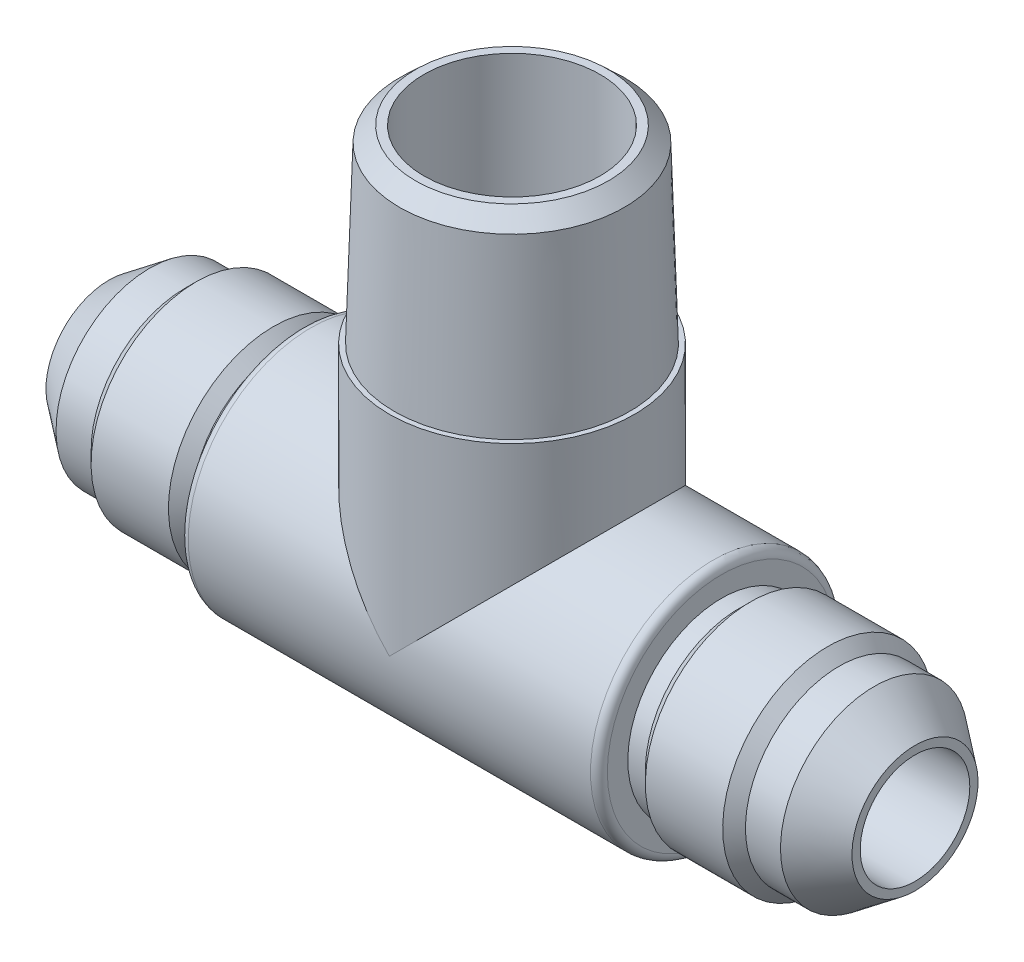
SolidWorks part; units mm, degrees
ref_plane "Front Plane" through (0, 0, 0) normal (0, 0, 1) x (1, 0, 0)
ref_plane "Top Plane" through (0, 0, 0) normal (0, 1, 0) x (1, 0, 0)
ref_plane "Right Plane" through (0, 0, 0) normal (1, 0, 0) x (0, 0, -1)
sketch "Sketch1" plane through (0, 0, 0) normal (0, 0, 1) x (1, 0, 0)
  line L0 (0, 0) -> (-18.9865, 0) construction
  line L1 (0, 0) -> (0, 18.9865) construction
  line L2 (-9.525, 18.9865) -> (9.525, 18.9865) construction
  line L3 (-18.9865, 9.525) -> (-18.9865, -9.525) construction
  line L6 (-36.5125, 9.525) -> (-36.5125, -9.525) construction
  line L8 (-10.668, 36.1163) -> (10.668, 36.1163) construction
  line L9 (0, 0) -> (0, 36.1163) construction
  line L10 (-18.9865, 11.1125) -> (-18.9865, -11.1125) construction
  line L12 (-11.1125, 18.9865) -> (11.1125, 18.9865) construction
  point P15 (0, 22.5603)
  dimension "S" = 17.526
  dimension "Pipe Thread Dia" = 21.336
  dimension "V" = 36.1163
  dimension "TE" = 13.556
  dimension "OA" = 22.225
ref_plane "Plane1" through (-36.5125, 0, 0) normal (1, 0, 0) x (0, 0, -1)
sketch "Sketch2" plane through (-36.5125, 0, 0) normal (1, 0, 0) x (0, 0, -1)
  circle A0 centre (0, 0) radius 9.525
  dimension "Thread OD" = 19.05
extrude "Extrude1" add sketch "Sketch2" along normal up to vertex (17.526 mm away) up to point (-18.9865, 0, 0)
sketch "Sketch3" plane through (-36.5125, 0, 0) normal (-1, 0, 0) x (0, 0, 1)
  circle A0 centre (0, 0) radius 9.525 construction
  circle A1 centre (0, 0) radius 9.525
curve "Helix/Spiral1" pitch 1.5875 height 36.5125 turns 23 parameters "pitch"=1.5875
sketch "Sketch4" plane through (0, 0, 0) normal (0, 0, 1) x (1, 0, 0)
  line L0 (-37.9016, 9.525) -> (-37.3062, 8.4939)
  line L1 (-37.3062, 8.4939) -> (-37.1078, 8.4939)
  line L2 (-37.1078, 8.4939) -> (-36.5125, 9.525)
  line L3 (-37.9016, 9.525) -> (-36.5125, 9.525)
  line L6 (-37.207, 9.525) -> (-37.207, 8.4939) construction
  line L7 (-37.6039, 9.0094) -> (-36.8102, 9.0094) construction
  line L8 (-36.5125, 9.525) -> (-36.5125, -9.525) construction
  dimension "D1" = 0.1984
  dimension "D2" = 0.7937
  dimension "D3" = 60
sweep "Cut-Sweep1" [suppressed] cut profiles "Sketch4" path "Helix/Spiral1"
sketch "Sketch5" plane through (0, 0, 0) normal (0, 0, 1) x (1, 0, 0)
  line L0 (-36.5125, 6.35) -> (-36.5125, -6.35) construction
  line L1 (-32.8189, 8.4939) -> (-29.6439, 8.4939)
  line L2 (-29.6439, 8.4939) -> (-28.6128, 9.525)
  line L3 (-36.5125, 5.7106) -> (-36.5125, -5.7106) construction
  line L4 (-28.6128, 9.525) -> (-36.5125, 9.525)
  line L5 (-37.9016, 9.525) -> (-36.5125, 9.525) construction
  line L6 (-18.9865, 9.525) -> (-18.9865, -9.525) construction
  line L7 (-18.9865, 8.4939) -> (-20.574, 8.4939)
  line L8 (-20.574, 8.4939) -> (-21.6051, 9.525)
  line L9 (-21.6051, 9.525) -> (-18.9865, 9.525)
  line L10 (-18.9865, 8.4939) -> (-18.9865, 9.525)
  line L11 (-27.2626, -9.525) -> (-27.2626, 0) construction
  line L12 (-18.9865, 0) -> (-36.5125, 0) construction
  line L13 (-36.5125, 9.525) -> (-36.5125, -9.525) construction
  line L14 (-36.5125, 5.7106) -> (-32.8189, 8.4939)
  line L15 (-36.5125, 9.525) -> (-36.5125, 5.7106)
  line L16 (0, 0) -> (-18.9865, 0) construction
  point P16 (-27.2626, -9.525)
  dimension "D3" = 45
  dimension "D5" = 45
  dimension "D6" = 1.5875
  dimension "Tube OD" = 12.7
  dimension "D2" = 11.4211
  dimension "D1" = 37
  dimension "D4" = 3.175
  dimension "D7" = 2.3813
revolve "Cut-Revolve1" cut sketch "Sketch5" angle 360 about L0
ref_plane "Plane2" through (-18.9865, 0, 0) normal (1, 0, 0) x (0, 0, -1)
sketch "Sketch15" plane through (-18.9865, 0, 0) normal (1, 0, 0) x (0, 0, -1)
  circle A0 centre (0, 0) radius 11.1125
extrude "Boss-Extrude1" add sketch "Sketch15" along normal up to vertex (18.9865 mm away) up to point (0, 0, 0)
sketch "Sketch16" plane through (0, 0, 0) normal (1, 0, 0) x (0, 0, -1)
  circle A0 centre (0, 0) radius 4.9657
  dimension "Min ID" = 9.9314
extrude "Cut-Extrude1" cut sketch "Sketch16" against normal through all
ref_plane "Plane3" through (0, 18.9865, 0) normal (0, 1, 0) x (-1, 0, 0)
sketch "Sketch20" plane through (0, 18.9865, 0) normal (0, 1, 0) x (-1, 0, 0)
  circle A0 centre (0, 0) radius 11.1125
extrude "Boss-Extrude2" add sketch "Sketch20" against normal up to vertex (18.9865 mm away) separate body up to point (0, 0, 0)
sketch "Sketch22" plane through (0, 18.9865, 0) normal (0, 1, 0) x (-1, 0, 0)
  circle A0 centre (0, 0) radius 10.668
extrude "Boss-Extrude3" add sketch "Sketch22" along normal up to vertex (17.1298 mm away) draft 1.75 separate body up to point (0, 36.1163, 0)
sketch "Sketch23" plane through (0, 36.1163, 0) normal (0, 1, 0) x (1, 0, 0)
  circle A0 centre (0, 0) radius 10.1446 construction
  circle A1 centre (0, 0) radius 10.1446
curve "Helix/Spiral2" parameters "Pitch"=1.8143
chamfer "Chamfer1" distance 1.3607 angle 45 1 edges at (0, 36.1163, 10.1446) first distance on face at (0, 36.1163, 10.1446)
sketch "Sketch25" plane through (0, 18.9865, 0) normal (0, -1, 0) x (1, 0, 0)
  circle A1 centre (0, 0) radius 10.668
  circle A2 centre (0, 0) radius 10.668
  dimension "D1" = 0
sketch "Sketch24" plane through (0, 0, 0) normal (0, 0, 1) x (1, 0, 0)
  line L0 (10.2428, 37.8738) -> (10.2428, 36.0596) construction
  line L1 (10.2428, 36.0596) -> (8.6716, 36.9667) construction
  line L2 (8.6716, 36.9667) -> (10.2428, 37.8738) construction
  line L3 (8.868, 37.0801) -> (8.868, 36.8533)
  line L4 (8.6716, 36.9667) -> (8.868, 36.9667) construction
  line L5 (10.0464, 37.7605) -> (10.0464, 36.173) construction
  line L6 (10.0464, 36.9667) -> (10.2428, 36.9667) construction
  line L7 (10.1446, 36.9667) -> (10.1446, 36.1163) construction
  line L8 (10.1446, 37.8172) -> (10.2428, 36.0596)
  line L9 (10.2428, 36.0596) -> (8.868, 36.8533)
  line L10 (8.868, 37.0801) -> (10.1446, 37.8172)
  dimension "D1" = 1.8143
  dimension "D2" = 0.2268
sweep "Cut-Sweep2" [suppressed] cut profiles "Sketch24" path "Helix/Spiral2"
extrude "Boss-Extrude4" add sketch "Sketch25" against normal up to vertex (17.1298 mm away) draft 15 up to point (10.668, 36.1163, 0)
sketch "Sketch28" plane through (0, 36.1163, 0) normal (0, 1, 0) x (1, 0, 0)
  circle A2 centre (0, 0) radius 7.9784
  circle A3 centre (0, 0) radius 7.9784
  dimension "D1" = 0.762
extrude "Cut-Extrude6" cut sketch "Sketch28" against normal up to vertex (17.1298 mm away) up to point (0, 18.9865, 0)
fillet "Fillet1" radius 0.762 1 edges at (-18.9865, 0, -11.1125)
sketch "Sketch10" plane through (0, 0, 0) normal (1, 0, 0) x (0, 0, -1)
  line L0 (0, 0) -> (-12.651, 0) construction
ref_axis "Axis1" through (0, 0, 12.651) along (0, 0, -1)
pattern_circular "CirPattern1" count 2 over 180 about axis through (0, 0, 12.651) along (0, 0, -1) reverse direction yes of bodies 110 103
combine bodies "Combine2" operation type add bodies to combine 110 122 114 105
sketch "Sketch30" plane through (0, 0, 0) normal (0, 0, 1) x (1, 0, 0)
  line L0 (0, 18.9865) -> (0, 9.4932)
  line L1 (0, 18.9865) -> (-10.922, 18.9865)
  line L2 (0, 0) -> (0, 18.9865) construction
  line L3 (-10.922, 18.9865) -> (0, 9.4932) construction
  line L4 (-5.461, 14.2399) -> (-6.1275, 13.4731) construction
  line L5 (-10.922, 18.9865) -> (-10.922, 18.4785)
  arc A0 (-10.922, 18.4785) -> (0, 9.4932) centre (13.649, 37.215) ccw
  point P2 (0, 9.4932)
  dimension "D1" = 0.254
  dimension "D2" = 1.016
  dimension "D3" = 0.508
revolve "Revolve1" add sketch "Sketch30" angle 360 about L0
sketch "Sketch26" plane through (-36.5125, 0, 0) normal (-1, 0, 0) x (0, 0, 1)
  circle A0 centre (0, 0) radius 4.9657 construction
  circle A1 centre (0, 0) radius 4.9657
extrude "Cut-Extrude4" cut sketch "Sketch26" against normal through all
sketch "Sketch29" plane through (0, 0, 0) normal (0, 1, 0) x (1, 0, 0)
  circle A0 centre (0, 0) radius 4.9657
  dimension "D1" = 9.9314
extrude "Cut-Extrude7" cut sketch "Sketch29" along normal through all
sketch "Sketch12" plane through (0, 0, 0) normal (0, 0, 1) x (1, 0, 0)
  line L0 (0, 0) -> (0, 36.1163) construction
  line L2 (0, 0) -> (-36.5125, 0) construction
  line L3 (7.9784, 36.1163) -> (-7.9784, 36.1163) construction
sketch "Sketch13" plane through (0, 0, 0) normal (1, 0, 0) x (0, 0, -1)
  line L0 (9.525, 18.9865) -> (-9.525, 18.9865)
  line L1 (0, 0) -> (0, 18.9865) construction
  line L3 (9.525, 0) -> (-9.525, 0)
  circle A0 centre (0, 0) radius 4.9657
  circle A1 centre (0, 0) radius 4.9657 construction
  dimension "D1" = 19.05
equation "\"D1@Sketch1\" = \"Thread OD@Sketch2\""
equation "\"D3@Helix/Spiral1\" = \"Q@Sketch1\""
equation "\"D1@Sketch4\" = \"pitch@Helix/Spiral1\"*.125"
equation "\"D2@Sketch4\" = \"pitch@Helix/Spiral1\"*.5"
equation "\"D6@Sketch5\" = \"pitch@Helix/Spiral1\"*1"
equation "\"D4@Sketch5\" = \"pitch@Helix/Spiral1\"*2"
equation "\"D1@Sketch13\" = \"D1@Sketch1\""
equation "\"D7@Sketch5\" = \"pitch@Helix/Spiral1\"*1.5"
equation "\"D2@Sketch5\" = \"Min ID@Sketch16\"*1.15"
equation "\"D1@Sketch24\" = \"Pitch@Helix/Spiral2\""
equation "\"D2@Sketch24\" = \"Pitch@Helix/Spiral2\"/8"
equation "\"D1@Chamfer1\" = \"Pitch@Helix/Spiral2\"*.750"
equation "\"D1@Sketch29\" =  \"Min ID@Sketch16\""
